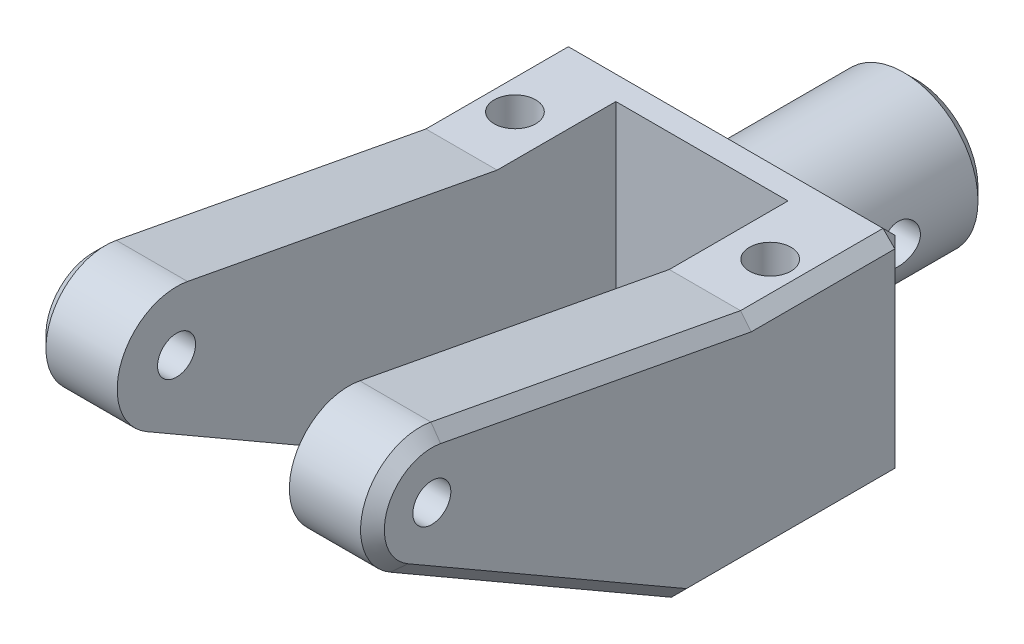
SolidWorks part; units mm, degrees
ref_plane "正面(Front)" through (0, 0, 0) normal (0, 0, 1) x (1, 0, 0)
ref_plane "平面(Top)" through (0, 0, 0) normal (0, 1, 0) x (1, 0, 0)
ref_plane "右側面(Right)" through (0, 0, 0) normal (1, 0, 0) x (0, 0, -1)
sketch "ｽｹｯﾁ1" plane through (0, 0, 0) normal (0, 0, 1) x (1, 0, 0)
  circle A0 centre (0, 0) radius 6.25
  dimension "D1" = 12.5
extrude "ﾎﾞｽ - 押し出し1" add sketch "ｽｹｯﾁ1" along normal blind 15
sketch "ｽｹｯﾁ2" plane through (0, 0, 15) normal (0, 0, 1) x (1, 0, 0)
  line L1 (-14.25, 9) -> (14.25, 9)
  line L2 (-14.25, 9) -> (-14.25, -9)
  line L3 (-14.25, -9) -> (14.25, -9)
  line L4 (14.25, 9) -> (14.25, -9)
  line L5 (-14.25, 9) -> (14.25, -9) construction
  line L6 (-14.25, -9) -> (14.25, 9) construction
  point P0 (0, 0)
  dimension "D1" = 18
  dimension "D2" = 28.5
extrude "ﾎﾞｽ - 押し出し2" add sketch "ｽｹｯﾁ2" along normal blind 3
sketch "ｽｹｯﾁ4" plane through (0, 0, 0) normal (1, 0, 0) x (0, 0, -1)
  line L0 (-18, 9) -> (-42.311, 9) construction
  line L2 (-54.0741, 13.9135) -> (-28, 9)
  line L3 (-28, 9) -> (-18, 9)
  line L5 (-18, 9) -> (-18, -9)
  line L6 (-18, -9) -> (-18, 9) construction
  line L7 (-56.6248, 4.2713) -> (-18, -9)
  line L8 (-18, -9) -> (-15, -9) construction
  arc A0 (-54.0741, 13.9135) -> (-56.6248, 4.2713) centre (-55, 9) ccw
  circle A1 centre (-55, 9) radius 1.6
  dimension "D2" = 5
  dimension "D1" = 3.2
  dimension "D3" = 37
  dimension "D4" = 10
extrude "ﾎﾞｽ - 押し出し3" add sketch "ｽｹｯﾁ4" against normal blind 7 from surface starting at face at (14.25, 0, 16.5)
extrude "ﾎﾞｽ - 押し出し4" add sketch "ｽｹｯﾁ4<2>" along normal blind 7 from surface starting at face at (-14.25, 0, 16.5)
sketch "ｽｹｯﾁ4<2>" plane through (0, 0, 0) normal (1, 0, 0) x (0, 0, -1) same geometry as "ｽｹｯﾁ4"
sketch "ｽｹｯﾁ5" plane through (-14.25, 0, 0) normal (-1, 0, 0) x (0, 0, 1)
  line L0 (18, -9) -> (33.8231, -9)
  line L1 (33.8231, -9) -> (57.5, 4.6699)
  line L2 (56.6248, 4.2713) -> (18, -9) construction
  line L3 (56.6248, 4.2713) -> (18, -9)
  arc A0 (56.6248, 4.2713) -> (54.0741, 13.9135) centre (55, 9) ccw construction
  arc A1 (56.6248, 4.2713) -> (57.5, 4.6699) centre (55, 9) ccw
  dimension "D1" = 30
extrude "ﾎﾞｽ - 押し出し5" add sketch "ｽｹｯﾁ5" against normal blind 7
mirror "ﾐﾗｰ1" about plane through (0, 0, 0) normal (1, 0, 0) of "ﾎﾞｽ - 押し出し5"
sketch "ｽｹｯﾁ7" plane through (0, 9, 0) normal (0, 1, 0) x (1, 0, 0)
  line L0 (10.75, -28) -> (10.75, -12.373) construction
  line L1 (7.25, -28) -> (14.25, -28) construction
  line L2 (7.25, -18) -> (-7.25, -18) construction
  line L3 (0, 0) -> (0, -40.3817) construction
  circle A0 centre (10.75, -23) radius 1.75
  circle A1 centre (-10.75, -23) radius 1.75
  dimension "D1" = 3.5
  dimension "D2" = 5
extrude "ｶｯﾄ - 押し出し1" cut sketch "ｽｹｯﾁ7" against normal through all
chamfer "面取り1" distance 1 angle 45 14 edges at (-14.25, -2.1651, 45.6615) (14.25, -2.1651, 45.6615) (-14.25, 10.7376, 59.6884) (14.25, 10.7376, 59.6884) (0, -9, 15) (-14.25, -9, 24.4115) (-14.25, 0, 15) (-14.25, 11.4568, 41.037) (-14.25, 9, 21.5) (0, 9, 15) (14.25, -9, 24.4115) (14.25, 0, 15) (14.25, 9, 21.5) (14.25, 11.4568, 41.037)
chamfer "面取り2" distance 1 angle 45 1 edges at (6.25, 0, 0)
sketch "ｽｹｯﾁ8" plane through (0, 0, 0) normal (1, 0, 0) x (0, 0, -1)
  line L0 (0, 0) -> (-14.2374, 0) construction
  line L1 (0, -5.25) -> (0, 5.25) construction
  circle A0 centre (-7.5, 0) radius 1.65
  point P5 (-7.4804, 0)
  dimension "D1" = 7.5
  dimension "D2" = 3.3
extrude "ｶｯﾄ - 押し出し2" cut sketch "ｽｹｯﾁ8" against normal through all both and the other way through all
